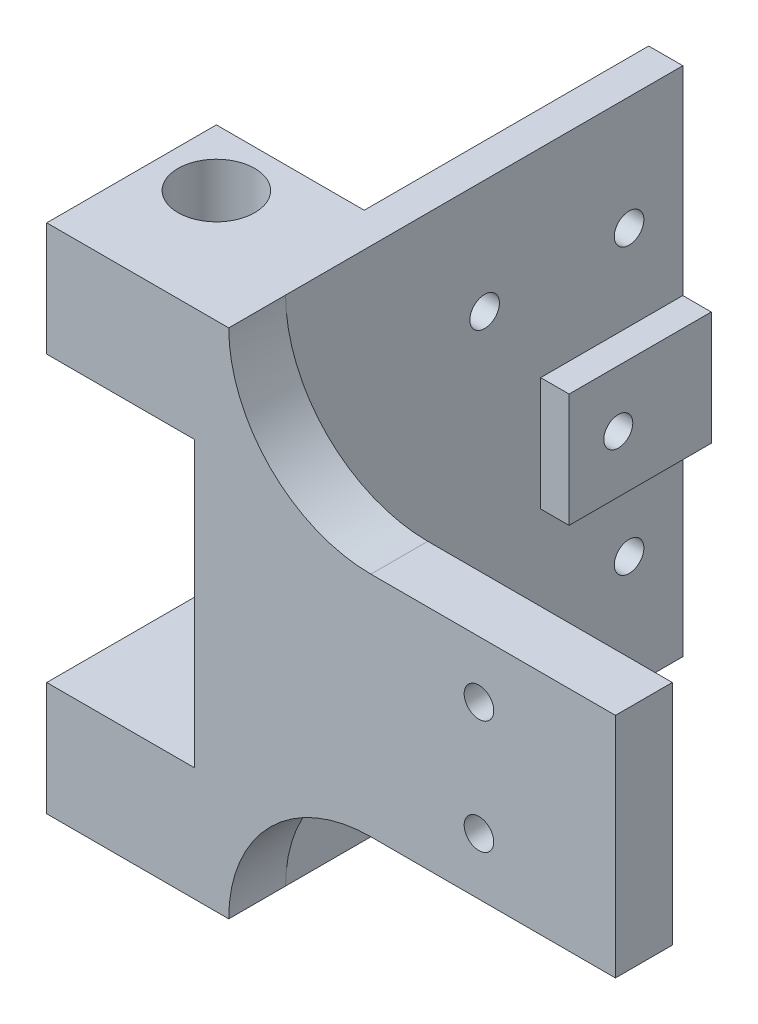
SolidWorks part; units mm, degrees
ref_plane "Front Plane" through (0, 0, 0) normal (0, 0, 1) x (1, 0, 0)
ref_plane "Top Plane" through (0, 0, 0) normal (0, 1, 0) x (1, 0, 0)
ref_plane "Right Plane" through (0, 0, 0) normal (1, 0, 0) x (0, 0, -1)
sketch "Sketch1" plane through (0, 0, 0) normal (0, 0, 1) x (1, 0, 0)
  line L1 (0, 0) -> (74, 0)
  line L2 (0, 0) -> (0, 90)
  line L3 (0, 90) -> (74, 90)
  line L4 (74, 0) -> (74, 90)
  circle A0 centre (50, 55) radius 2.6
  circle A1 centre (50, 35) radius 2.6
  dimension "D3" = 5.2
  dimension "D4" = 5.2
  dimension "D1" = 90
  dimension "D2" = 74
  dimension "D5" = 50
  dimension "D6" = 50
  dimension "D7" = 20
  dimension "D8" = 35
extrude "Boss-Extrude1" add sketch "Sketch1" along normal blind 10
sketch "Sketch2" plane through (0, 0, 0) normal (0, 0, -1) x (-1, 0, 0)
  line L0 (0, 0) -> (-74, 0) construction
  line L1 (0, 90) -> (-6, 90)
  line L2 (0, 90) -> (0, 0)
  line L3 (0, 0) -> (-6, 0)
  line L4 (-6, 90) -> (-6, 0)
  dimension "D1" = 6
extrude "Boss-Extrude2" add sketch "Sketch2" along normal blind 69.85
sketch "Sketch4" plane through (0, 0, 0) normal (0, 0, -1) x (-1, 0, 0)
  line L0 (-6, 90) -> (-6, 0) construction
  line L1 (-74, 90) -> (-6, 90)
  line L2 (-74, 90) -> (-74, 65)
  line L3 (-74, 65) -> (-6, 65)
  line L4 (-6, 90) -> (-6, 65)
  line L5 (-6, 90) -> (-6, 0) construction
  line L6 (-74, 0) -> (-6, 0)
  line L7 (-74, 0) -> (-74, 25)
  line L8 (-74, 25) -> (-6, 25)
  line L9 (-6, 0) -> (-6, 25)
  dimension "D1" = 25
  dimension "D2" = 25
extrude "Cut-Extrude3" cut sketch "Sketch4" against normal through all
fillet "Fillet2" radius 25 2 edges at (6, 65, 5) (6, 25, 5)
sketch "Sketch8" plane through (0, 0, 0) normal (-1, 0, 0) x (0, 0, 1)
  line L0 (10, 90) -> (10, 0) construction
  line L1 (10, 0) -> (-19.83, 0)
  line L2 (10, 0) -> (10, 20)
  line L3 (10, 20) -> (-19.83, 20)
  line L4 (-19.83, 0) -> (-19.83, 20)
  line L5 (10, 90) -> (-69.85, 90) construction
  line L6 (-19.83, 70) -> (10, 70)
  line L7 (-19.83, 70) -> (-19.83, 90)
  line L8 (-19.83, 90) -> (10, 90)
  line L9 (10, 70) -> (10, 90)
  dimension "D1" = 20
  dimension "D2" = 0
  dimension "D3" = 29.83
  dimension "D4" = 0
  dimension "D5" = 0
  dimension "D6" = 20
  dimension "D7" = 29.83
extrude "Boss-Extrude4" add sketch "Sketch8" along normal blind 26
sketch "Sketch9" plane through (0, 0, 0) normal (0, -1, 0) x (1, 0, 0)
  line L0 (-26, -19.83) -> (0, -19.83) construction
  line L1 (-26, -19.83) -> (-26, 10) construction
  circle A0 centre (-16, -9.83) radius 6.75
  dimension "D1" = 13.5
  dimension "D2" = 10
  dimension "D3" = 10
extrude "Cut-Extrude6" cut sketch "Sketch9" against normal blind 10
sketch "Sketch10" plane through (0, 90, 0) normal (0, 1, 0) x (1, 0, 0)
  line L0 (-26, -10) -> (-26, 19.83) construction
  line L1 (-26, 19.83) -> (0, 19.83) construction
  circle A0 centre (-16, 9.83) radius 6.75
  dimension "D1" = 13.5
  dimension "D2" = 10
  dimension "D3" = 10
extrude "Cut-Extrude7" cut sketch "Sketch10" against normal blind 10
sketch "Sketch11" plane through (0, 0, 0) normal (-1, 0, 0) x (0, 0, 1)
  line L0 (-19.83, 90) -> (-69.85, 90) construction
  line L1 (10, 70) -> (10, 20) construction
  circle A0 centre (-53.5, 45) radius 6.35
  dimension "D2" = 63.5
  dimension "D3" = 12.7
  dimension "D1" = 45
extrude "Cut-Extrude8" cut sketch "Sketch11" against normal blind 4.9784
sketch "Sketch12" plane through (6, 0, 0) normal (1, 0, 0) x (0, 0, -1)
  line L0 (69.85, 90) -> (69.85, 0) construction
  line L1 (44.85, 55) -> (69.85, 55)
  line L2 (44.85, 55) -> (44.85, 35)
  line L3 (44.85, 35) -> (69.85, 35)
  line L4 (69.85, 55) -> (69.85, 35)
  line L5 (69.85, 90) -> (0, 90) construction
  dimension "D1" = 20
  dimension "D2" = 35
  dimension "D3" = 25
extrude "Boss-Extrude5" add sketch "Sketch12" along normal blind 5
sketch "Sketch13" plane through (4.9784, 0, 0) normal (-1, 0, 0) x (0, 0, 1)
  circle A0 centre (-53.5, 45) radius 2.55
  circle A1 centre (-53.5, 45) radius 6.35 construction
  dimension "D1" = 5.1
  dimension "D2" = 0
extrude "Cut-Extrude9" cut sketch "Sketch13" against normal through all both and the other way through all
sketch "Sketch14" plane through (0, 0, 0) normal (-1, 0, 0) x (0, 0, 1)
  line L0 (10, 70) -> (10, 20) construction
  line L1 (-19.83, 90) -> (-69.85, 90) construction
  line L2 (-19.83, 0) -> (-69.85, 0) construction
  circle A0 centre (-35, 70) radius 2.6
  circle A1 centre (-35, 20) radius 2.6
  circle A2 centre (-60.4, 70) radius 2.6
  circle A3 centre (-60.4, 20) radius 2.6
  dimension "D1" = 5.2
  dimension "D2" = 5.2
  dimension "D3" = 45
  dimension "D4" = 45
  dimension "D7" = 5.2
  dimension "D8" = 5.2
  dimension "D5" = 20
  dimension "D6" = 20
  dimension "D9" = 25.4
  dimension "D10" = 25.4
  dimension "D11" = 20
  dimension "D12" = 20
extrude "Cut-Extrude10" cut sketch "Sketch14" against normal through all
equation "\"D6@Sketch1\"=\"D5@Sketch1\""
equation "\"D8@Sketch1\"=(\"D1@Sketch1\"-\"D7@Sketch1\")/2"
equation "\"D3@Sketch7\"=(30-\"D1@Sketch7\")/2"
